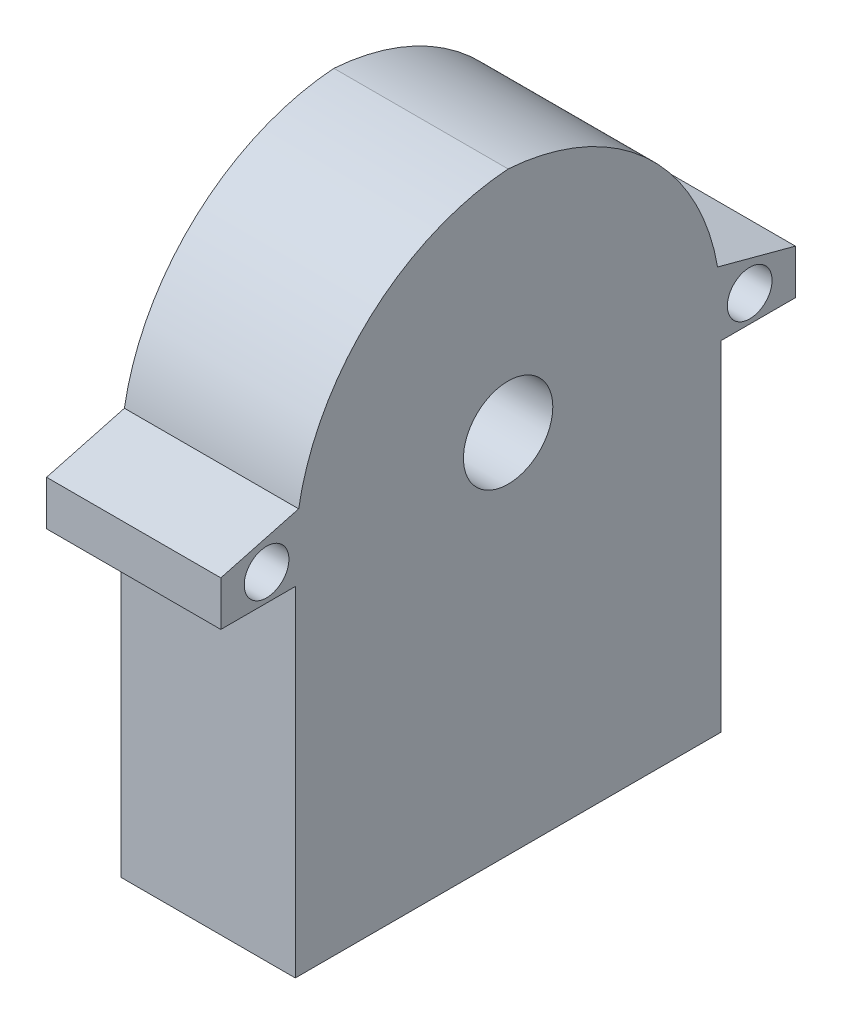
SolidWorks part; units mm, degrees
ref_plane "Front Plane" through (0, 0, 0) normal (0, 0, 1) x (1, 0, 0)
ref_plane "Top Plane" through (0, 0, 0) normal (0, 1, 0) x (1, 0, 0)
ref_plane "Right Plane" through (0, 0, 0) normal (1, 0, 0) x (0, 0, -1)
sketch "Sketch2" plane through (0, 0, 0) normal (1, 0, 0) x (0, 0, -1)
  line L0 (-42.3673, 20.8964) -> (-42.3673, -19.0436)
  line L1 (-42.3673, -19.0436) -> (-13.7873, -19.0436)
  line L2 (-13.7873, -19.0436) -> (-13.7873, 20.8964)
  line L3 (-13.7873, 20.8964) -> (-42.3673, 20.8964)
  dimension "D1" = 28.58
  dimension "D2" = 39.94
extrude "Boss-Extrude1" add sketch "Sketch2" along normal blind 11.7
fillet "Fillet1" radius 15.4 2 edges at (5.85, 20.8964, 13.7873) (5.85, 20.8964, 42.3673)
sketch "Sketch3" plane through (11.7, 0, 0) normal (1, 0, 0) x (0, 0, -1)
  circle A0 centre (-44.2973, 5.5264) radius 1.5
  circle A1 centre (-11.8573, 5.5264) radius 1.5
  dimension "D1" = 3
  dimension "D2" = 3
  dimension "D3" = 15.33
  dimension "D4" = 0
  dimension "D5" = 16.22
  dimension "D6" = 16.22
sketch "Sketch5" plane through (11.7, 0, 0) normal (1, 0, 0) x (0, 0, -1)
  line L0 (-42.1416, 8.1237) -> (-47.3673, 6.7234)
  line L1 (-47.3673, 6.7234) -> (-47.3673, 3.7234)
  line L2 (-47.3673, 3.7234) -> (-42.3673, 3.7234)
  line L3 (-42.3673, 5.4964) -> (-42.3673, -19.0436) construction
  line L4 (-13.7873, 3.7234) -> (-8.7873, 3.7234)
  line L5 (-13.7873, -19.0436) -> (-13.7873, 5.4964) construction
  line L6 (-8.7873, 3.7234) -> (-8.7873, 6.7234)
  line L7 (-8.7873, 6.7234) -> (-14.0131, 8.1237)
  line L8 (-42.3673, 3.7234) -> (-42.1416, 8.1237)
  line L9 (-13.7873, 3.7234) -> (-14.0131, 8.1237)
  arc A0 (-28.0773, 20.8564) -> (-42.3673, 5.4964) centre (-26.9673, 5.4964) ccw construction
  arc A1 (-13.7873, 5.4964) -> (-28.0773, 20.8564) centre (-29.1873, 5.4964) ccw construction
  dimension "D1" = 5
  dimension "D2" = 3
  dimension "D3" = 75
  dimension "D4" = 5.2258
  dimension "D5" = 5
  dimension "D6" = 3
  dimension "D7" = 105
extrude "Boss-Extrude2" add sketch "Sketch5" against normal blind 11.7
extrude "Cut-Extrude1" cut sketch "Sketch3" against normal blind 11.7
sketch "Sketch6" plane through (11.7, 0, 0) normal (1, 0, 0) x (0, 0, -1)
  circle A0 centre (-28.0773, 5.5264) radius 3
  point P2 (0, 0)
  point P6 (-59.3864, 25.5567)
  point P15 (-4.4655, 5.124)
  dimension "D1" = 6
  dimension "D3" = 0
  dimension "D2" = 15.33
extrude "Cut-Extrude2" cut sketch "Sketch6" against normal blind 11.7
